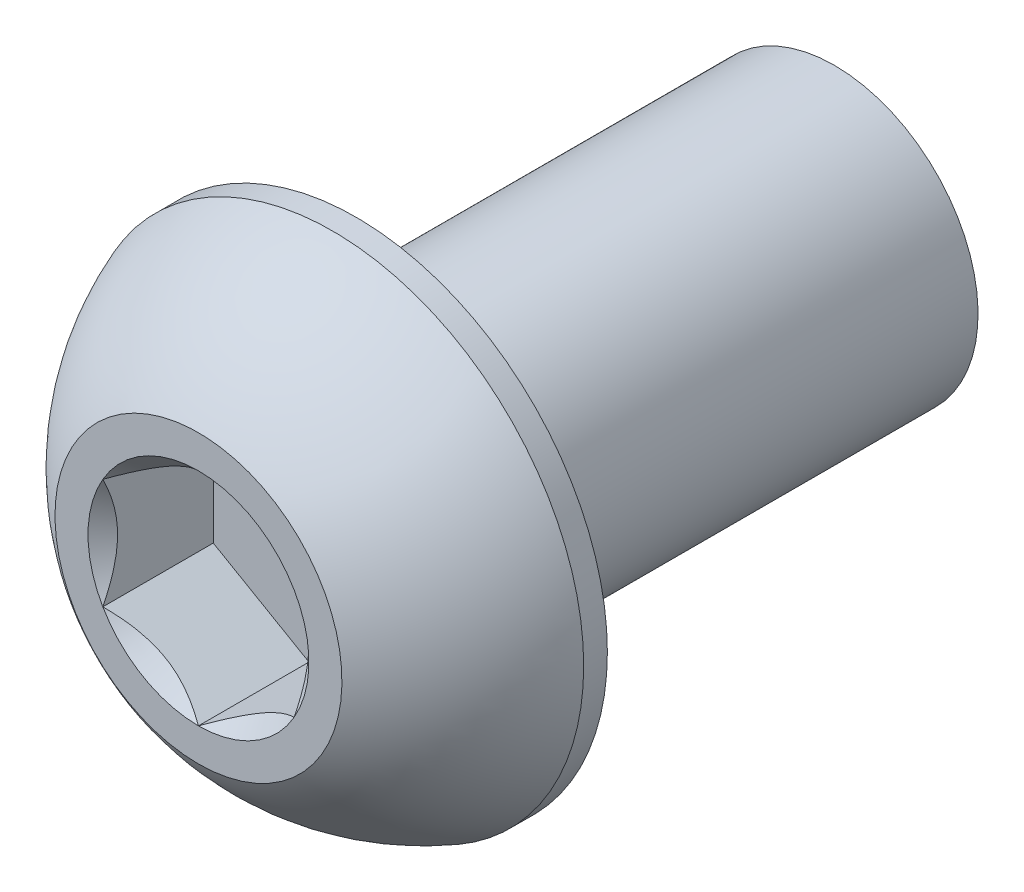
SolidWorks part; units mm, degrees
ref_plane "Front" through (0, 0, 0) normal (0, 0, 1) x (1, 0, 0)
ref_plane "Top" through (0, 0, 0) normal (0, 1, 0) x (1, 0, 0)
ref_plane "Right" through (0, 0, 0) normal (1, 0, 0) x (0, 0, -1)
sketch "Sketch1" plane through (0, 0, 0) normal (1, 0, 0) x (0, 0, -1)
  line L2 (3.3, 3) -> (13.3, 3)
  line L3 (13.3, 3) -> (13.3, 0)
  line L4 (13.3, 0) -> (3.3, 0)
  line L6 (2.805, 5.25) -> (3.3, 5.25) construction
  line L7 (13.3, 3) -> (13.3, -3) construction
  line L8 (0, 0) -> (3.3, 0) construction
  line L9 (3.3, 5.25) -> (3.3, -5.25) construction
  line L11 (3.3, 3) -> (3.3, 0)
  line L13 (0, 2) -> (0, -2) construction
  line L14 (0, 2) -> (0, 3) construction
  line L15 (13.3, -3) -> (12.3, -3) construction
  arc A3 (0, 3) -> (2.805, 5.25) centre (4.7113, 0) cw construction
  dimension "D1" = 0.495
  dimension "Pitch" = 1
revolve "Revolve1" add sketch "Sketch1" angle 360 mid plane about L4
sketch "Sketch7" plane through (0, 0, 0) normal (1, 0, 0) x (0, 0, -1)
  line L6 (2.805, 5.25) -> (3.3, 5.25) construction
  line L8 (0, 0) -> (3.3, 0) construction
  line L11 (3.3, 5.25) -> (3.3, -5.25) construction
  line L12 (2.805, 5.25) -> (3.3, 5.25)
  line L13 (0, 0) -> (3.3, 0)
  line L14 (0, 2) -> (0, -2) construction
  line L15 (3.3, 5.25) -> (3.3, 0)
  line L16 (0, 3) -> (0, 0)
  arc A2 (2.805, 5.25) -> (0, 3) centre (4.7113, 0) ccw construction
  arc A3 (2.805, 5.25) -> (0, 3) centre (4.7113, 0) ccw
revolve "Revolve2" add sketch "Sketch7" angle 360 mid plane about L13
sketch "Sketch5" plane through (0, 0, 0) normal (0, 0, 1) x (1, 0, 0)
  line L1 (2, -1.1547) -> (2, 1.1547)
  line L2 (2, 1.1547) -> (0, 2.3094)
  line L3 (0, 2.3094) -> (-2, 1.1547)
  line L4 (-2, 1.1547) -> (-2, -1.1547)
  line L5 (-2, -1.1547) -> (0, -2.3094)
  line L6 (0, -2.3094) -> (2, -1.1547)
  circle A0 centre (0, 0) radius 2 construction
extrude "Cut-Extrude2" cut sketch "Sketch5" against normal blind 2.31
sketch "Sketch6" plane through (0, 0, 0) normal (0, 0, 1) x (1, 0, 0)
  circle A0 centre (0, 0) radius 2.3094
extrude "Cut-Extrude3" cut sketch "Sketch6" against normal blind 2.31 draft 45
sketch "Sketch11" plane through (0, 0, 0) normal (1, 0, 0) x (0, 0, -1)
  line L0 (3.3, -5.25) -> (3.3, 5.25)
  point P4 (3.3, 0)
split "Split1" trim tools "Sketch11" bodies to split 113 resulting bodies 119 120
sketch "Sketch10" plane through (0, 0, 0) normal (1, 0, 0) x (0, 0, -1)
  line L0 (13.3, 3) -> (13.3, -3) construction
  point P0 (11.8, -3)
  dimension "D1" = 1.5
sketch "Sketch3" [suppressed] plane through (0, 0, -13.3) normal (0, 0, -1) x (-1, 0, 0)
  circle A0 centre (0, 0) radius 3
curve "Helix/Spiral1" [suppressed] pitch 1 height 11 turns 11
sketch "Sketch2" [suppressed] plane through (0, 0, 0) normal (1, 0, 0) x (0, 0, -1)
  line L0 (13.2375, 3.1083) -> (14.2375, 3.1083) construction
  line L1 (14.2375, 3.1083) -> (13.7375, 2.2422) construction
  line L2 (13.7375, 2.2422) -> (13.2375, 3.1083) construction
  line L3 (13.7375, 3.1083) -> (13.7375, 3) construction
  line L4 (13.7375, 3) -> (13.7375, 2.3505) construction
  line L5 (13.7375, 2.3505) -> (13.7375, 2.2422) construction
  line L6 (13.675, 2.3505) -> (13.8, 2.3505)
  line L7 (13.3, 3) -> (14.175, 3) construction
  line L8 (13.2687, 3.0541) -> (14.2062, 3.0541)
  line L9 (13.2687, 3.0541) -> (13.675, 2.3505)
  line L10 (14.2062, 3.0541) -> (13.8, 2.3505)
  point P10 (13.7375, 2.3505)
  point P13 (13.7375, 3)
  point P16 (13.7375, 3.0541)
  dimension "D1" = 1
  dimension "D2" = 0.125
chamfer "Chamfer1" [suppressed] distance 0.75 angle 45
sweep "Cut-Sweep1" [suppressed] cut profiles "Sketch2" path "Helix/Spiral1"
combine bodies "Combine1" [suppressed] operation type add bodies to combine 120 114
equation "\"D3@Helix/Spiral1\" = \"Lg@Sketch1\" + \"D4@Helix/Spiral1\""
equation "\"D1@Chamfer1\" = \"D4@Helix/Spiral1\" * .75"
equation "\"D1@Cut-Extrude2\" = \"Head Ht@Sketch1\" * .7"
equation "\"D1@Sketch1\" = \"Head Ht@Sketch1\" * .15"
equation "\"D1@Sketch10\" = \"D4@Helix/Spiral1\" * 1.5"
equation "\"D1@Cut-Extrude3\" = \"D1@Cut-Extrude2\""
equation "\"D4@Helix/Spiral1\"=\"Pitch@Sketch1\""
equation "\"D1@Sketch2\"=\"Pitch@Sketch1\""
equation "\"D2@Sketch2\"=\"D1@Sketch2\"/8"
